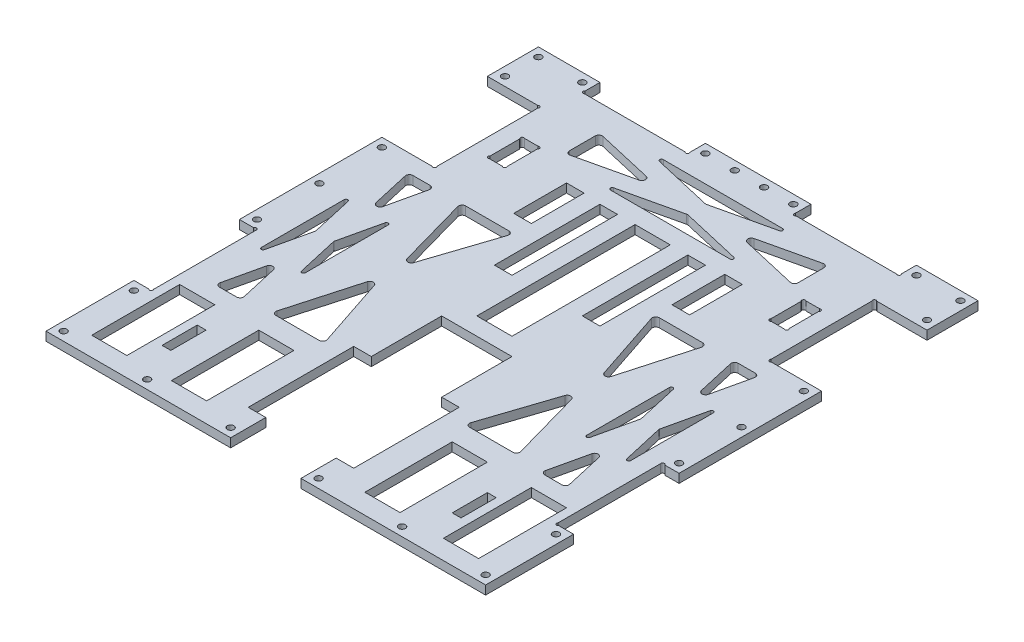
SolidWorks part; units mm, degrees
material "7050-T73510"
ref_plane "Front Plane" through (0, 0, 0) normal (0, 0, 1) x (1, 0, 0)
ref_plane "Top Plane" through (0, 0, 0) normal (0, 1, 0) x (1, 0, 0)
ref_plane "Right Plane" through (0, 0, 0) normal (1, 0, 0) x (0, 0, -1)
sketch "Sketch1" plane through (0, 0, 0) normal (0, 1, 0) x (1, 0, 0)
  line L1 (-158.75, -177.8) -> (158.75, -177.8)
  line L2 (-158.75, -177.8) -> (-158.75, 177.8)
  line L3 (-158.75, 177.8) -> (158.75, 177.8)
  line L4 (158.75, -177.8) -> (158.75, 177.8)
  line L5 (-158.75, -177.8) -> (158.75, 177.8) construction
  line L6 (-158.75, 177.8) -> (158.75, -177.8) construction
  point P0 (0, 0)
  dimension "D1" = 355.6
  dimension "D2" = 317.5
extrude "Boss-Extrude1" add sketch "Sketch1" along normal blind 6.35
sketch "Sketch2" plane through (0, 6.35, 0) normal (0, 1, 0) x (1, 0, 0)
  line L0 (-158.75, -177.8) -> (158.75, -177.8) construction
  line L1 (-25.4, -25.4) -> (25.4, -25.4)
  line L2 (-25.4, -25.4) -> (-25.4, -177.8)
  line L3 (-25.4, -177.8) -> (25.4, -177.8)
  line L4 (25.4, -25.4) -> (25.4, -177.8)
  line L5 (-25.4, -25.4) -> (25.4, -177.8) construction
  line L6 (-25.4, -177.8) -> (25.4, -25.4) construction
  point P0 (0, -101.6)
  dimension "D1" = 152.4
  dimension "D2" = 50.8
extrude "Cut-Extrude1" cut sketch "Sketch2" against normal through all
sketch "Sketch3" plane through (0, 6.35, 0) normal (0, 1, 0) x (1, 0, 0)
  line L0 (158.75, -177.8) -> (158.75, 177.8) construction
  line L5 (146.05, 140.97) -> (120.65, 140.97)
  line L11 (146.05, 140.97) -> (146.05, 64.77)
  line L13 (146.05, 64.77) -> (120.65, 64.77)
  line L15 (120.65, 140.97) -> (120.65, 64.77)
  line L16 (158.75, 177.8) -> (-158.75, 177.8) construction
  line L17 (107.95, 90.17) -> (95.25, 90.17)
  line L18 (107.95, 90.17) -> (107.95, 115.57)
  line L19 (107.95, 115.57) -> (95.25, 115.57)
  line L20 (95.25, 90.17) -> (95.25, 115.57)
  line L21 (0, -3.4925) -> (0, 3.4925) construction
  line L22 (-95.25, 90.17) -> (-95.25, 115.57)
  line L23 (-107.95, 115.57) -> (-95.25, 115.57)
  line L24 (-107.95, 90.17) -> (-107.95, 115.57)
  line L25 (-107.95, 90.17) -> (-95.25, 90.17)
  line L26 (-120.65, 140.97) -> (-120.65, 64.77)
  line L27 (-146.05, 64.77) -> (-120.65, 64.77)
  line L28 (-146.05, 140.97) -> (-146.05, 64.77)
  line L29 (-146.05, 140.97) -> (-120.65, 140.97)
  point P14 (107.95, 102.87)
  point P15 (120.65, 102.87)
  dimension "D1" = 25.4
  dimension "D2" = 12.7
  dimension "D3" = 12.7
  dimension "D4" = 12.7
  dimension "D5" = 25.4
  dimension "D6" = 76.2
  dimension "D7" = 36.83
extrude "Cut-Extrude2" cut sketch "Sketch3" against normal through all contours L5 L15 L13 L11 | L20 L17 L18 L19 | L29 L28 L27 L26 | L24 L25 L22 L23 | L26 L27 L28 L29 region at (133.35, 6.35, -102.87) region at (101.6, 6.35, -102.87) region at (-101.6, 6.35, -102.87) region at (-133.35, 6.35, -102.87)
sketch "Sketch4" plane through (0, 6.35, 0) normal (0, 1, 0) x (1, 0, 0)
  line L0 (-158.75, 177.8) -> (-158.75, -177.8) construction
  line L1 (-158.75, 140.97) -> (-146.05, 140.97)
  line L2 (-158.75, 140.97) -> (-158.75, 64.77)
  line L3 (-158.75, 64.77) -> (-146.05, 64.77)
  line L4 (-146.05, 140.97) -> (-146.05, 64.77)
  line L5 (0, -3.4925) -> (0, 3.4925) construction
  line L6 (-158.75, -114.3) -> (-146.05, -114.3)
  line L7 (-158.75, -114.3) -> (-158.75, -38.1)
  line L8 (-158.75, -38.1) -> (-146.05, -38.1)
  line L9 (-146.05, -114.3) -> (-146.05, -38.1)
  line L10 (158.75, 64.77) -> (146.05, 64.77)
  line L11 (146.05, 140.97) -> (146.05, 64.77)
  line L12 (158.75, 140.97) -> (146.05, 140.97)
  line L13 (158.75, 140.97) -> (158.75, 64.77)
  line L14 (158.75, -38.1) -> (146.05, -38.1)
  line L15 (146.05, -114.3) -> (146.05, -38.1)
  line L16 (158.75, -114.3) -> (146.05, -114.3)
  line L17 (158.75, -114.3) -> (158.75, -38.1)
  line L18 (158.75, 177.8) -> (-158.75, 177.8) construction
  line L19 (114.3, 165.1) -> (38.1, 165.1)
  line L20 (-114.3, 177.8) -> (-38.1, 177.8)
  line L21 (-114.3, 177.8) -> (-114.3, 165.1)
  line L22 (-114.3, 165.1) -> (-38.1, 165.1)
  line L23 (-38.1, 177.8) -> (-38.1, 165.1)
  line L24 (38.1, 177.8) -> (38.1, 165.1)
  line L25 (114.3, 177.8) -> (38.1, 177.8)
  line L26 (114.3, 177.8) -> (114.3, 165.1)
  line L27 (-25.4, -25.4) -> (-25.4, -177.8) construction
  line L28 (-25.4, -152.4) -> (-38.1, -152.4)
  line L29 (-25.4, -152.4) -> (-25.4, -76.2)
  line L30 (-25.4, -76.2) -> (-38.1, -76.2)
  line L31 (-38.1, -152.4) -> (-38.1, -76.2)
  line L32 (-158.75, -177.8) -> (-25.4, -177.8) construction
  line L33 (25.4, 101.6) -> (38.1, 101.6)
  line L34 (-25.4, 25.4) -> (-38.1, 25.4)
  line L35 (-25.4, 25.4) -> (-25.4, 101.6)
  line L36 (-25.4, 101.6) -> (-38.1, 101.6)
  line L37 (-38.1, 25.4) -> (-38.1, 101.6)
  line L38 (38.1, 25.4) -> (38.1, 101.6)
  line L39 (25.4, 25.4) -> (38.1, 25.4)
  line L40 (25.4, 25.4) -> (25.4, 101.6)
  line L41 (25.4, -76.2) -> (38.1, -76.2)
  line L42 (38.1, -152.4) -> (38.1, -76.2)
  line L43 (25.4, -152.4) -> (38.1, -152.4)
  line L44 (25.4, -152.4) -> (25.4, -76.2)
  dimension "D1" = 12.7
  dimension "D2" = 12.7
  dimension "D3" = 76.2
  dimension "D4" = 76.2
  dimension "D5" = 36.83
  dimension "D6" = 215.9
  dimension "D7" = 12.7
  dimension "D8" = 76.2
  dimension "D9" = 76.2
  dimension "D10" = 12.7
  dimension "D11" = 76.2
  dimension "D12" = 25.4
  dimension "D13" = 76.2
  dimension "D14" = 12.7
  dimension "D15" = 203.2
  dimension "D16" = 50.8
extrude "Cut-Extrude3" cut sketch "Sketch4" against normal through all
sketch "Sketch5" plane through (0, 6.35, 0) normal (0, 1, 0) x (1, 0, 0)
  line L0 (-38.1, -76.2) -> (-38.1, -152.4) construction
  line L5 (-38.1, 101.6) -> (-38.1, 25.4) construction
  line L6 (-82.55, -100.33) -> (-57.15, -100.33)
  line L7 (-133.35, -87.63) -> (-101.6, -87.63)
  line L8 (-133.35, -87.63) -> (-133.35, 52.07)
  line L9 (-133.35, 52.07) -> (-101.6, 52.07)
  line L10 (-101.6, -87.63) -> (-101.6, 52.07)
  line L11 (-133.35, -87.63) -> (-101.6, 52.07) construction
  line L12 (-133.35, 52.07) -> (-101.6, -87.63) construction
  line L13 (-82.55, 114.3) -> (82.55, 114.3)
  line L14 (-82.55, 114.3) -> (-82.55, 152.4)
  line L15 (-82.55, 152.4) -> (82.55, 152.4)
  line L16 (82.55, 114.3) -> (82.55, 152.4)
  line L17 (-82.55, 114.3) -> (82.55, 152.4) construction
  line L18 (-82.55, 152.4) -> (82.55, 114.3) construction
  line L23 (0, -3.4925) -> (0, 3.4925) construction
  line L24 (-12.7, -12.7) -> (12.7, -12.7)
  line L25 (-146.05, -114.3) -> (-146.05, -38.1) construction
  line L26 (-50.8, 102.87) -> (-63.5, 102.87)
  line L27 (-50.8, 102.87) -> (-50.8, 64.77)
  line L28 (-158.75, 64.77) -> (-158.75, -38.1) construction
  line L29 (-158.75, 64.77) -> (-120.65, 64.77) construction
  line L30 (-82.55, -100.33) -> (-82.55, -163.4194)
  line L31 (-12.7, -12.7) -> (-12.7, 101.6)
  line L32 (-12.7, 101.6) -> (12.7, 101.6)
  line L33 (12.7, -12.7) -> (12.7, 101.6)
  line L34 (-50.8, 64.77) -> (-63.5, 64.77)
  line L35 (-63.5, 102.87) -> (-63.5, 64.77)
  line L36 (50.8, 64.77) -> (63.5, 64.77)
  line L37 (-25.4, 25.4) -> (-25.4, 101.6) construction
  line L38 (-25.4, 101.6) -> (-38.1, 101.6) construction
  line L39 (-95.25, 90.17) -> (-95.25, 115.57) construction
  line L40 (-114.3, 165.1) -> (-38.1, 165.1) construction
  line L41 (-82.55, -163.4194) -> (-57.15, -163.4194)
  line L42 (-57.15, -100.33) -> (-57.15, -163.4194)
  line L43 (-139.5421, 50.6627) -> (-107.7921, -89.0373)
  line L44 (-127.1579, -89.0373) -> (-95.4079, 50.6627)
  line L45 (63.5, 102.87) -> (63.5, 64.77)
  line L46 (50.8, 102.87) -> (63.5, 102.87)
  line L47 (-83.9779, 146.2126) -> (81.1221, 108.1126)
  line L48 (-81.1221, 108.1126) -> (83.9779, 146.2126)
  line L49 (50.8, 102.87) -> (50.8, 64.77)
  line L50 (-88.9, -16.4414) -> (-50.8, -16.4414) construction
  line L51 (-127.1579, 53.4773) -> (-95.4079, -86.2227)
  line L52 (-139.5421, -86.2227) -> (-107.7921, 53.4773)
  line L53 (-88.9, 52.07) -> (-50.8, 52.07) construction
  line L54 (-88.9, 52.07) -> (-88.9, -84.9527) construction
  line L55 (-81.1221, 158.5874) -> (83.9779, 120.4874)
  line L56 (-83.9779, 120.4874) -> (81.1221, 158.5874)
  line L57 (-139.7, -100.33) -> (-114.3, -100.33)
  line L58 (-139.7, -100.33) -> (-139.7, -163.83)
  line L59 (-139.7, -163.83) -> (-114.3, -163.83)
  line L60 (-114.3, -100.33) -> (-114.3, -163.83)
  line L61 (-88.9, -84.9527) -> (-50.8, -84.9527)
  line L62 (-50.8, 52.07) -> (-50.8, -84.9527) construction
  line L63 (-107.95, -144.78) -> (-101.6, -144.78)
  line L64 (-107.95, -144.78) -> (-107.95, -119.38)
  line L65 (-107.95, -119.38) -> (-101.6, -119.38)
  line L66 (-101.6, -144.78) -> (-101.6, -119.38)
  line L67 (-107.95, -144.78) -> (-101.6, -119.38) construction
  line L68 (-107.95, -119.38) -> (-101.6, -144.78) construction
  line L69 (-88.9, -84.9527) -> (-71.4375, -22.7914)
  line L70 (-71.4375, -22.7914) -> (-50.8, -84.9527)
  line L71 (-88.9, 52.07) -> (-50.8, 52.07)
  line L72 (-88.9, 52.07) -> (-71.4375, -10.0914)
  line L73 (-71.4375, -10.0914) -> (-50.8, 52.07)
  point P5 (-117.475, -17.78)
  point P10 (0, 133.35)
  point P15 (0, 44.45)
  point P34 (-104.775, -132.08)
  point P45 (-31.75, 101.6)
  point P87 (-114.3, -132.08)
  dimension "D3" = 12.7
  dimension "D4" = 19.05
  dimension "D5" = 139.7
  dimension "D6" = 25.4
  dimension "D7" = 12.7
  dimension "D8" = 31.75
  dimension "D9" = 25.4
  dimension "D10" = 12.7
  dimension "D11" = 165.1
  dimension "D12" = 12.7
  dimension "D13" = 12.7
  dimension "D14" = 12.7
  dimension "D17" = 25.4
  dimension "D18" = 63.5
  dimension "D19" = 12.7
  dimension "D20" = 6.35
  dimension "D21" = 38.1
  dimension "D22" = 38.1
  dimension "D23" = 25.4
  dimension "D15" = 114.3
  dimension "D16" = 12.7
  dimension "D24" = 12.7
  dimension "D25" = 12.7
  dimension "D26" = 12.7
  dimension "D27" = 15.3773
  dimension "D28" = 12.7
  dimension "D29" = 6.35
  dimension "D30" = 12.7
extrude "Cut-Extrude4" cut sketch "Sketch5" against normal through all contours L44 L7 L43 | L8 L52 L43 | L51 L52 L9 | L44 L51 L10 | L33 | L32 | L31 | L24 | L48 L13 L47 | L48 L55 L16 | L55 L56 L15 | L14 L56 L47 | L60 L57 L58 L59 | L63 L66 L65 L64 | L42 L6 L30 L41 | L26 L35 L34 L27 | L46 L49 L36 L45 | L61 L70 L69 | L71 L73 L72 region at (-69.85, 6.35, 131.8747) region at (-117.475, 6.35, 73.8975) region at (-130.229, 6.35, 17.78) region at (-104.721, 6.35, 17.78) region at (-117.475, 6.35, -38.3375) region at (0, 6.35, -118.4777) region at (-64.4466, 6.35, -133.35) region at (64.4466, 6.35, -133.35) region at (0, 6.35, -148.2223) region at (0, 6.35, -44.45) region at (-57.15, 6.35, -83.82) region at (57.15, 6.35, -83.82) region at (-127, 6.35, 132.08) region at (-104.775, 6.35, 132.08)
mirror "Mirror1" about plane through (0, 0, 0) normal (1, 0, 0) of "Cut-Extrude4"
sketch "Sketch7" plane through (0, 6.35, 0) normal (0, 1, 0) x (1, 0, 0)
  line L0 (-158.75, -177.8) -> (-25.4, -177.8) construction
  line L1 (-158.75, -114.3) -> (-158.75, -177.8) construction
  line L2 (0, -3.4925) -> (0, 3.4925) construction
  line L3 (-158.75, 177.8) -> (-158.75, 140.97) construction
  line L4 (-114.3, 177.8) -> (-158.75, 177.8) construction
  line L6 (38.1, 177.8) -> (-38.1, 177.8) construction
  line L7 (-38.1, 165.1) -> (-38.1, 177.8) construction
  line L8 (-25.4, -152.4) -> (-25.4, -177.8) construction
  line L9 (-158.75, -114.3) -> (-146.05, -114.3) construction
  line L10 (-158.75, 64.77) -> (-158.75, -38.1) construction
  line L11 (-146.05, -38.1) -> (-158.75, -38.1) construction
  line L12 (-158.75, 64.77) -> (-120.65, 64.77) construction
  circle A0 centre (-152.4, -171.45) radius 2.413
  circle A14 centre (-152.4, 171.45) radius 2.413
  circle A15 centre (-120.65, 171.45) radius 2.413
  circle A16 centre (-152.4, 147.32) radius 2.413
  circle A34 centre (-31.75, 171.45) radius 2.413
  circle A35 centre (-10.5833, 171.45) radius 2.413
  circle A36 centre (10.5833, 171.45) radius 2.413
  circle A37 centre (31.75, 171.45) radius 2.413
  circle A38 centre (-31.75, -171.45) radius 2.413
  circle A39 centre (-92.075, -171.45) radius 2.413
  circle A40 centre (-152.4, -120.65) radius 2.413
  circle A41 centre (-152.4, -31.75) radius 2.413
  circle A42 centre (-152.4, 58.42) radius 2.413
  circle A43 centre (-152.4, 13.335) radius 2.413
  circle A44 centre (31.75, -171.45) radius 2.413
  circle A45 centre (152.4, 13.335) radius 2.413
  circle A46 centre (152.4, 58.42) radius 2.413
  circle A47 centre (152.4, -31.75) radius 2.413
  circle A48 centre (152.4, -120.65) radius 2.413
  circle A49 centre (92.075, -171.45) radius 2.413
  circle A50 centre (152.4, 147.32) radius 2.413
  circle A51 centre (120.65, 171.45) radius 2.413
  circle A52 centre (152.4, 171.45) radius 2.413
  circle A53 centre (152.4, -171.45) radius 2.413
  dimension "D1" = 4.826
  dimension "D6" = 6.35
  dimension "D9" = 4.826
  dimension "D14" = 4.826
  dimension "D4" = 4.826
  dimension "D5" = 4.826
  dimension "D8" = 4.826
  dimension "D20" = 4.826
  dimension "D24" = 4.826
  dimension "D25" = 4.826
  dimension "D2" = 6.35
  dimension "D3" = 6.35
  dimension "D7" = 60.325
  dimension "D10" = 6.35
  dimension "D11" = 6.35
  dimension "D15" = 6.35
  dimension "D16" = 6.35
  dimension "D18" = 6.35
  dimension "D19" = 6.35
  dimension "D21" = 6.35
  dimension "D22" = 6.35
  dimension "D23" = 6.35
  dimension "D26" = 45.085
  dimension "D12" = 2
  dimension "D13" = 2
  dimension "D17" = 4
extrude "Cut-Extrude6" cut sketch "Sketch7" against normal through all
sketch "Sketch8" plane through (0, 6.35, 0) normal (0, 1, 0) x (1, 0, 0)
  circle A0 centre (-39.0994, 165.8837) radius 1.27
  circle A1 centre (-113.5398, 166.1174) radius 1.27
  circle A2 centre (-121.56, 140.0841) radius 1.27
  circle A3 centre (-121.5656, 65.6501) radius 1.27
  circle A4 centre (-147.253, -38.507) radius 1.27
  circle A5 centre (-147.0444, -113.51) radius 1.27
  circle A6 centre (-107.1943, 114.5493) radius 1.27
  circle A7 centre (-96.0341, 114.5709) radius 1.27
  circle A8 centre (-107.1845, 91.1833) radius 1.27
  circle A10 centre (-96.2084, 91.0033) radius 1.27
extrude "Cut-Extrude7" cut sketch "Sketch8" against normal through all
mirror "Mirror2" about plane through (0, 0, 0) normal (1, 0, 0) of "Cut-Extrude7"
fillet "Fillet1" radius 1.27 16 edges at (-101.6, 3.175, 58.9775) (-110.9631, 3.175, 17.78) (-101.6, 3.175, -23.4175) (-133.35, 3.175, -23.4175) (-123.9869, 3.175, 17.78) (-133.35, 3.175, 58.9775) (133.35, 3.175, -23.4175) (133.35, 3.175, 58.9775) (123.9869, 3.175, 17.78) (101.6, 3.175, -23.4175) (110.9631, 3.175, 17.78) (101.6, 3.175, 58.9775) (54.3101, 3.175, -152.4) (-54.3101, 3.175, -152.4) (54.3101, 3.175, -114.3) (-54.3101, 3.175, -114.3)
fillet "Fillet2" radius 2.54 32 edges at (-126.8381, 3.175, 87.63) (-108.1119, 3.175, 87.63) (-117.475, 3.175, 46.4325) (-28.2399, 3.175, -133.35) (-82.55, 3.175, -120.8169) (-82.55, 3.175, -145.8831) (-88.9, 3.175, -52.07) (-71.4375, 3.175, 10.0914) (-50.8, 3.175, -52.07) (-71.4375, 3.175, 22.7914) (-88.9, 3.175, 84.9527) (-50.8, 3.175, 84.9527) (-126.8381, 3.175, -52.07) (-117.475, 3.175, -10.8725) (-108.1119, 3.175, -52.07) (126.8381, 3.175, 87.63) (108.1119, 3.175, 87.63) (117.475, 3.175, 46.4325) (88.9, 3.175, 84.9527) (50.8, 3.175, 84.9527) (71.4375, 3.175, 22.7914) (117.475, 3.175, -10.8725) (108.1119, 3.175, -52.07) (126.8381, 3.175, -52.07) (71.4375, 3.175, 10.0914) (88.9, 3.175, -52.07) (50.8, 3.175, -52.07) (28.2399, 3.175, -133.35) (82.55, 3.175, -120.8169) (82.55, 3.175, -145.8831) (0, 3.175, -139.8669) (0, 3.175, -126.8331)
